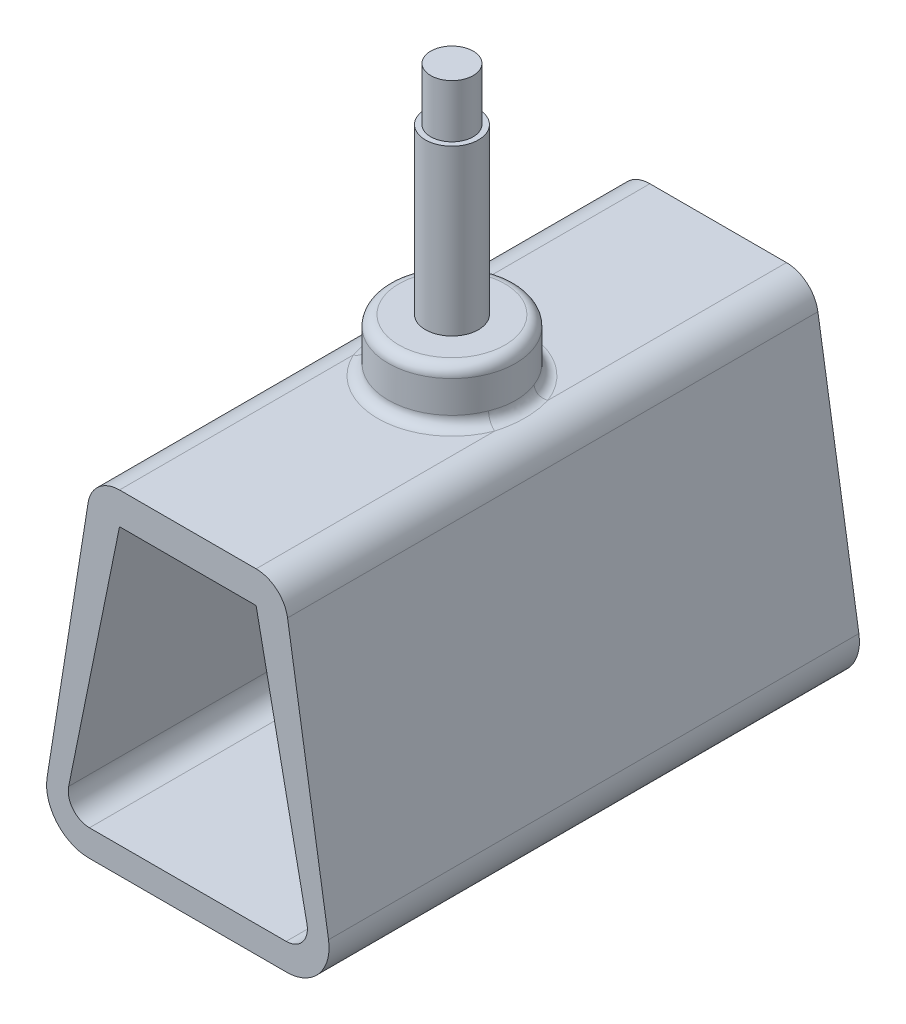
SolidWorks part; units mm, degrees
ref_plane "Alzado" through (0, 0, 0) normal (0, 0, 1) x (1, 0, 0)
ref_plane "Planta" through (0, 0, 0) normal (0, 1, 0) x (1, 0, 0)
ref_plane "Vista lateral" through (0, 0, 0) normal (1, 0, 0) x (0, 0, -1)
sketch "Croquis1" plane through (0, 0, 0) normal (0, 0, 1) x (1, 0, 0)
  line L0 (4.685, 0) -> (23.315, 0)
  line L1 (27.2655, 4.6271) -> (23.4015, 28.9703)
  line L2 (20.4386, 31.5) -> (7.5614, 31.5)
  line L3 (4.5985, 28.9703) -> (0.7345, 4.6271)
  line L4 (7.5614, 28.5) -> (20.4386, 28.5)
  line L5 (20.4386, 28.5) -> (25.2324, 4.8981)
  line L6 (23.2724, 2.5) -> (4.7276, 2.5)
  line L7 (2.7676, 4.8981) -> (7.5614, 28.5)
  arc A0 (23.315, 0) -> (27.2655, 4.6271) centre (23.315, 4) ccw
  arc A1 (4.685, 0) -> (0.7345, 4.6271) centre (4.685, 4) cw
  arc A2 (23.4015, 28.9703) -> (20.4386, 31.5) centre (20.4386, 28.5) ccw
  arc A3 (7.5614, 31.5) -> (4.5985, 28.9703) centre (7.5614, 28.5) ccw
  arc A4 (25.2324, 4.8981) -> (23.2724, 2.5) centre (23.2724, 4.5) cw
  arc A5 (4.7276, 2.5) -> (2.7676, 4.8981) centre (4.7276, 4.5) cw
  point P7 (28, 0)
  point P10 (0, 0)
  point P11 (22.8355, 16.699)
  point P15 (23, 31.5)
  point P18 (5, 31.5)
  point P20 (25.3335, 16.7987)
  point P21 (14, 0)
  point P22 (14, 2.5)
  point P23 (2.044, 2.5)
  dimension "D5" = 4
  dimension "D6" = 3
  dimension "D9" = 2
  dimension "D1" = 18
  dimension "D2" = 28
  dimension "D3" = 5
  dimension "D4" = 31.5
  dimension "D7" = 2.5
  dimension "D8" = 2.5
extrude "Saliente-Extruir1" add sketch "Croquis1" against normal blind 50
ref_plane "Plano1" through (0, 31.5, 0) normal (0, 1, 0) x (1, 0, 0)
sketch "Croquis2" plane through (0, 31.5, 0) normal (0, 1, 0) x (1, 0, 0)
  line L0 (20.4386, 50) -> (7.5614, 50) construction
  line L1 (23.4015, 50) -> (23.4015, 0) construction
  circle A0 centre (13.9015, 25) radius 6
  circle A1 centre (13.9015, 25) radius 2.5
  circle A2 centre (13.9015, 25) radius 2
  point P4 (14, 50)
  dimension "D2" = 12
  dimension "D4" = 5
  dimension "D3" = 9.5
  dimension "D5" = 4
  dimension "D1" = 25
extrude "Saliente-Extruir2" add sketch "Croquis2" along normal blind 5 contours A0 A1 region at (8.0712, 31.5, -25)
extrude "Saliente-Extruir3" add sketch "Croquis2<3>" along normal blind 15.5 from surface contours A1 starting at face at (13.9015, 36.5, -22.5)
sketch "Croquis2<3>" plane through (0, 31.5, 0) normal (0, 1, 0) x (1, 0, 0) same geometry as "Croquis2"
extrude "Saliente-Extruir4" add sketch "Croquis2<4>" along normal blind 5 from surface contours A2 starting at face at (13.9015, 52, -22.5)
sketch "Croquis2<4>" plane through (0, 31.5, 0) normal (0, 1, 0) x (1, 0, 0) same geometry as "Croquis2"
fillet "Redondeo1" radius 1 2 edges at (13.9015, 31.5, -19) (13.9015, 36.5, -19)
